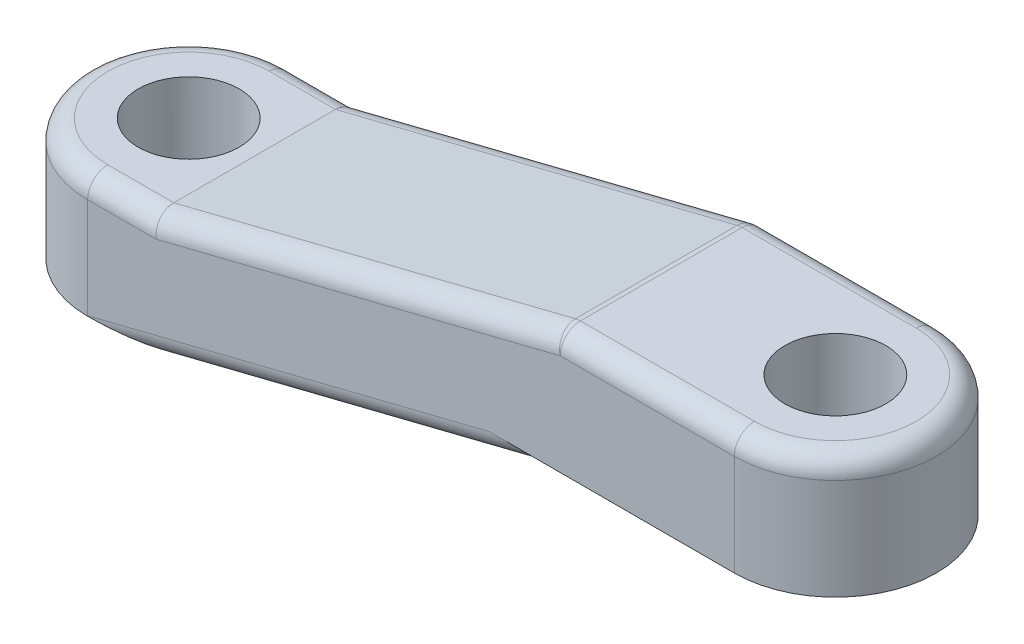
SolidWorks part; units mm, degrees
ref_plane "Front Plane" through (0, 0, 0) normal (0, 0, 1) x (1, 0, 0)
ref_plane "Top Plane" through (0, 0, 0) normal (0, 1, 0) x (1, 0, 0)
ref_plane "Right Plane" through (0, 0, 0) normal (1, 0, 0) x (0, 0, -1)
sketch "Sketch2" plane through (0, 0, 0) normal (0, 0, 1) x (1, 0, 0)
  line L0 (-5.08, 0) -> (0, 0)
  line L1 (0, 0) -> (25.4, 6.35)
  line L2 (25.4, 6.35) -> (35.56, 6.35)
  line L3 (-5.08, 7.62) -> (-0.9381, 7.62)
  line L4 (-0.9381, 7.62) -> (24.4619, 13.97)
  line L5 (24.4619, 13.97) -> (35.56, 13.97)
  line L6 (-5.08, 7.62) -> (-5.08, 0)
  line L7 (35.56, 13.97) -> (35.56, 6.35)
  dimension "D1" = 40.64
  dimension "D2" = 6.35
  dimension "D3" = 5.08
  dimension "D4" = 10.16
  dimension "D5" = 7.62
extrude "Boss-Extrude1" add sketch "Sketch2" along normal blind 12.7
sketch "Sketch3" plane through (0, 7.62, 0) normal (0, 1, 0) x (1, 0, 0)
  line L0 (-5.08, -12.7) -> (-5.08, 0) construction
  line L1 (-5.08, 0) -> (-5.08, -12.7)
  arc A0 (-5.08, 0) -> (-5.08, -12.7) centre (-5.08, -6.35) ccw
extrude "Boss-Extrude2" add sketch "Sketch3" against normal up to surface (7.62 mm away) up to face at (-2.54, 0, 6.35)
sketch "Sketch4" plane through (0, 13.97, 0) normal (0, 1, 0) x (1, 0, 0)
  line L0 (35.56, -12.7) -> (35.56, 0) construction
  line L1 (35.56, 0) -> (35.56, -12.7)
  arc A0 (35.56, -12.7) -> (35.56, 0) centre (35.56, -6.35) ccw
extrude "Boss-Extrude3" add sketch "Sketch4" against normal up to surface (7.62 mm away) up to face at (30.48, 6.35, 6.35)
sketch "Sketch5" plane through (0, 0, 0) normal (0, 1, 0) x (1, 0, 0)
  circle A0 centre (-5.08, -6.35) radius 3.175
  circle A1 centre (35.56, -6.35) radius 3.175
  arc A2 (-5.08, 0) -> (-5.08, -12.7) centre (-5.08, -6.35) ccw construction
  arc A3 (35.56, -12.7) -> (35.56, 0) centre (35.56, -6.35) ccw construction
  dimension "D1" = 6.35
extrude "Cut-Extrude1" cut sketch "Sketch5" along normal through all
fillet "Fillet1" radius 1.27 4 edges at (12.7, 3.175, 0) (11.7619, 10.795, 0) (12.7, 3.175, 12.7) (11.7619, 10.795, 12.7)
fillet "Fillet2" radius 1.27 9 edges at (-0.3909, 7.62, 0) (-0.3909, 7.62, 12.7) (41.91, 13.97, 6.35) (-11.43, 7.62, 6.35) (32.6291, 13.97, 12.7) (25.9956, 13.97, 12.328) (24.4619, 13.97, 6.35) (25.9956, 13.97, 0.372) (32.6291, 13.97, 0)
